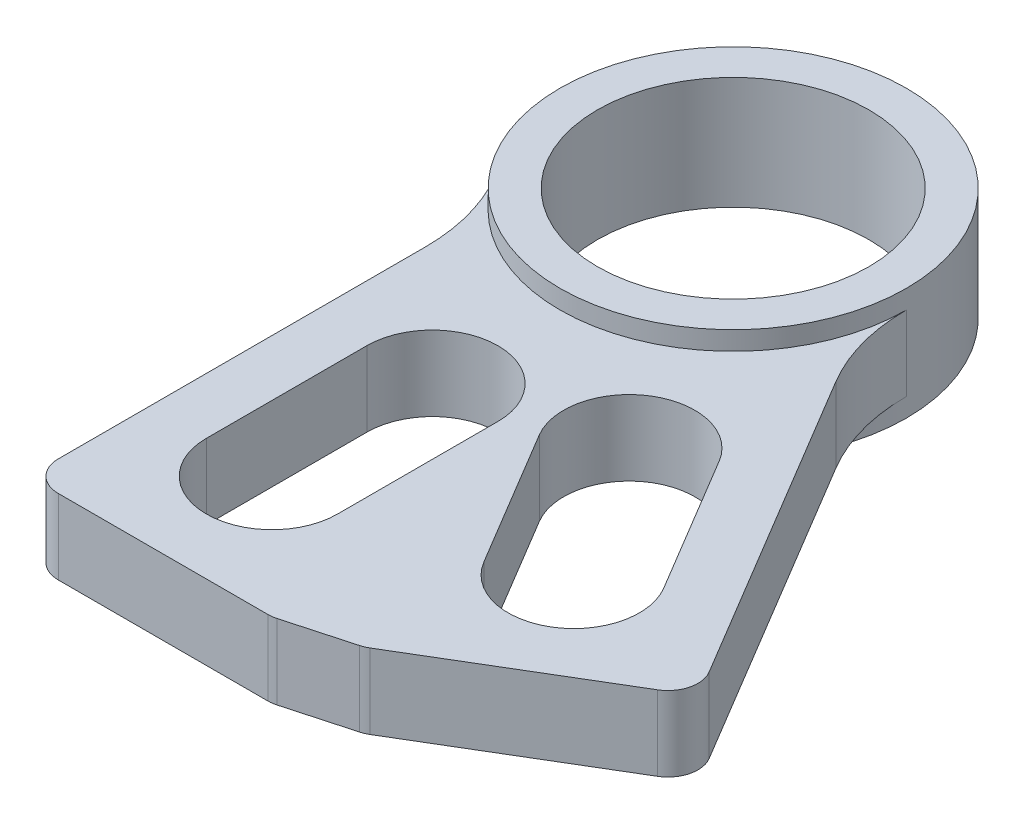
SolidWorks part; units mm, degrees
ref_plane "Front Plane" through (0, 0, 0) normal (0, 0, 1) x (1, 0, 0)
ref_plane "Top Plane" through (0, 0, 0) normal (0, 1, 0) x (1, 0, 0)
ref_plane "Right Plane" through (0, 0, 0) normal (1, 0, 0) x (0, 0, -1)
sketch "Sketch1" plane through (0, 0, 0) normal (0, 1, 0) x (1, 0, 0)
  line L0 (0, 0) -> (0, -49.3903) construction
  line L1 (0, 0) -> (25.3318, -42.3993) construction
  line L2 (0, -39.0716) -> (0, -25.4826) construction
  line L3 (-5.5562, -39.0716) -> (-5.5562, -25.4826)
  line L4 (5.5563, -39.0716) -> (5.5563, -25.4826)
  line L5 (20.0394, -33.5411) -> (13.0697, -21.8756) construction
  line L6 (15.2696, -36.3909) -> (8.3, -24.7254)
  line L7 (24.8092, -30.6914) -> (17.8395, -19.0259)
  line L8 (0, -49.3903) -> (0, -44.6278) construction
  line L9 (25.3318, -42.3993) -> (22.8891, -38.3109) construction
  line L10 (-10.3187, -49.3903) -> (10.3188, -49.3903)
  line L11 (16.4736, -47.6917) -> (34.19, -37.1069)
  line L12 (-10.3187, -49.3903) -> (-10.3187, -10.4432)
  line L13 (10.3188, -49.3903) -> (10.3188, -37.3899)
  line L14 (34.19, -37.1069) -> (14.2144, -3.6727)
  line L15 (16.4736, -47.6917) -> (10.3188, -37.3899)
  line L16 (185.3574, -310.2436) -> (14.7515, -24.6904) construction
  line L17 (10.3188, -49.3903) -> (16.4736, -47.6917)
  line L22 (0, 0) -> (10.3188, -37.3899) construction
  circle A0 centre (0, 0) radius 11.5062
  circle A1 centre (0, 0) radius 14.6812
  arc A2 (-5.5562, -39.0716) -> (5.5563, -39.0716) centre (0, -39.0716) ccw
  arc A3 (5.5563, -25.4826) -> (-5.5562, -25.4826) centre (0, -25.4826) ccw
  arc A4 (15.2696, -36.3909) -> (24.8092, -30.6914) centre (20.0394, -33.5411) ccw
  arc A5 (17.8395, -19.0259) -> (8.3, -24.7254) centre (13.0697, -21.8756) ccw
  point P8 (0, -32.2771)
  point P13 (16.5546, -27.7084)
  point P25 (0, -49.3903)
  point P27 (25.3318, -42.3993)
  dimension "D2" = 29.3624
  dimension "D3" = 4.7625
  dimension "D4" = 4.7625
  dimension "D5" = 13.589
  dimension "D6" = 49.3903
  dimension "D7" = 20.6375
extrude "Bearing_Insert_Extrude" add sketch "Sketch1" along normal mid plane 9.525 contours A1 A0 region at (-5.4988, 0, -13.1636)
extrude "Apex_Slot_Insert_Extrude" add sketch "Sketch1<4>" along normal mid plane 6.35 contours A1 L12 L10 L13 L15 L11 L14 A5 L7 A4 L6 A3 L4 A2 L3 | L13 L17 L15 region at (8.3278, 0, 30.1757) region at (12.3704, 0, 44.824)
sketch "Sketch1<4>" plane through (0, 0, 0) normal (0, 1, 0) x (1, 0, 0) same geometry as "Sketch1"
fillet "Fillet1" radius 16.002 2 edges at (14.2144, 0, 3.6727) (-10.3187, 0, 10.4432)
fillet "Fillet2" radius 2.54 4 edges at (34.19, 0, 37.1069) (-10.3187, 0, 49.3903) (16.4736, 0, 47.6917) (10.3188, 0, 49.3903)
equation "\"Apex_thickness\"= .25"
equation "\"Bearing_diameter\"= 0.906in"
equation "\"A-arm_angle\"= 39.1893"
equation "\"D1@Sketch1\"=\"Bearing_diameter\""
equation "\"D1@Apex_Slot_Insert_Extrude\"=\"Apex_thickness\""
